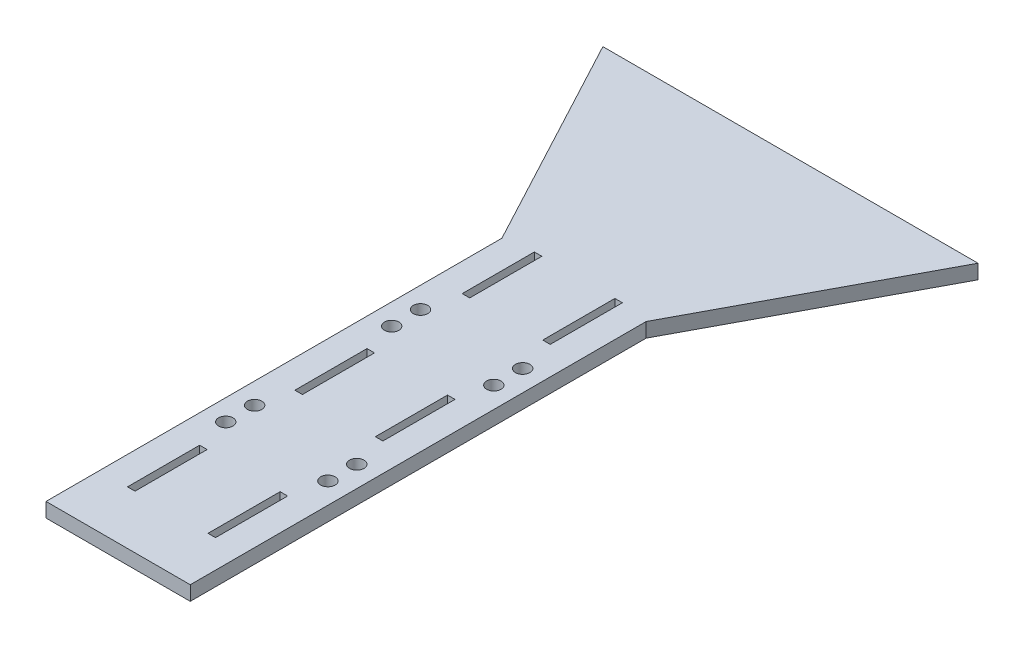
SolidWorks part; units mm, degrees
material "PC High Viscosity"
ref_plane "Front" through (0, 0, 0) normal (0, 0, 1) x (1, 0, 0)
ref_plane "Top" through (0, 0, 0) normal (0, 1, 0) x (1, 0, 0)
ref_plane "Right" through (0, 0, 0) normal (1, 0, 0) x (0, 0, -1)
sketch "Sketch1" plane through (0, 0, 0) normal (0, 1, 0) x (1, 0, 0)
  line L0 (-31.75, 0) -> (31.75, 0)
  line L1 (31.75, 0) -> (31.75, 200.66)
  line L2 (31.75, 200.66) -> (82.55, 295.91)
  line L3 (82.55, 295.91) -> (-82.55, 295.91)
  line L4 (-82.55, 295.91) -> (-31.75, 200.66)
  line L5 (-31.75, 200.66) -> (-31.75, 0)
  point P4 (0, 0)
  dimension "D1" = 63.5
  dimension "D2" = 200.66
  dimension "D3" = 95.25
  dimension "D4" = 165.1
extrude "Boss-Extrude1" add sketch "Sketch1" along normal blind 6.35
sketch "Sketch2" plane through (0, 6.35, 0) normal (0, 1, 0) x (1, 0, 0)
  line L0 (-19.304, 199.39) -> (-19.304, 173.99) construction
  line L1 (-19.304, 173.99) -> (-16.129, 173.99) construction
  line L2 (-16.129, 173.99) -> (-16.129, 199.39) construction
  line L3 (-16.129, 199.39) -> (-19.304, 199.39) construction
  line L4 (-19.304, 125.73) -> (-19.304, 100.33) construction
  line L5 (-19.304, 100.33) -> (-16.129, 100.33) construction
  line L6 (-16.129, 100.33) -> (-16.129, 125.73) construction
  line L7 (-16.129, 125.73) -> (-19.304, 125.73) construction
  line L12 (-19.304, 52.07) -> (-19.304, 26.67) construction
  line L13 (-19.304, 26.67) -> (-16.129, 26.67) construction
  line L14 (-16.129, 26.67) -> (-16.129, 52.07) construction
  line L15 (-16.129, 52.07) -> (-19.304, 52.07) construction
  line L20 (-19.304, 199.39) -> (-19.304, 173.99) construction
  line L21 (-19.304, 173.99) -> (-16.129, 173.99) construction
  line L22 (-16.129, 173.99) -> (-16.129, 199.39) construction
  line L23 (-16.129, 199.39) -> (-19.304, 199.39) construction
  line L24 (-19.304, 125.73) -> (-19.304, 100.33) construction
  line L25 (-19.304, 100.33) -> (-16.129, 100.33) construction
  line L26 (-16.129, 100.33) -> (-16.129, 125.73) construction
  line L27 (-16.129, 125.73) -> (-19.304, 125.73) construction
  line L32 (-19.304, 52.07) -> (-19.304, 26.67) construction
  line L33 (-19.304, 26.67) -> (-16.129, 26.67) construction
  line L34 (-16.129, 26.67) -> (-16.129, 52.07) construction
  line L35 (-16.129, 52.07) -> (-19.304, 52.07) construction
  line L36 (16.129, 52.07) -> (16.129, 26.67) construction
  line L37 (16.129, 26.67) -> (19.304, 26.67) construction
  line L38 (19.304, 26.67) -> (19.304, 52.07) construction
  line L39 (19.304, 52.07) -> (16.129, 52.07) construction
  line L44 (16.129, 125.73) -> (16.129, 100.33) construction
  line L45 (16.129, 100.33) -> (19.304, 100.33) construction
  line L46 (19.304, 100.33) -> (19.304, 125.73) construction
  line L47 (19.304, 125.73) -> (16.129, 125.73) construction
  line L48 (16.129, 199.39) -> (16.129, 173.99) construction
  line L49 (16.129, 173.99) -> (19.304, 173.99) construction
  line L50 (19.304, 173.99) -> (19.304, 199.39) construction
  line L51 (19.304, 199.39) -> (16.129, 199.39) construction
  line L56 (16.129, 52.07) -> (16.129, 26.67) construction
  line L57 (16.129, 26.67) -> (19.304, 26.67) construction
  line L58 (19.304, 26.67) -> (19.304, 52.07) construction
  line L59 (19.304, 52.07) -> (16.129, 52.07) construction
  line L60 (16.129, 125.73) -> (16.129, 100.33) construction
  line L61 (16.129, 100.33) -> (19.304, 100.33) construction
  line L62 (19.304, 100.33) -> (19.304, 125.73) construction
  line L63 (19.304, 125.73) -> (16.129, 125.73) construction
  line L68 (16.129, 199.39) -> (16.129, 173.99) construction
  line L69 (16.129, 173.99) -> (19.304, 173.99) construction
  line L70 (19.304, 173.99) -> (19.304, 199.39) construction
  line L71 (19.304, 199.39) -> (16.129, 199.39) construction
  line L72 (-19.3675, 23.495) -> (-19.304, 26.67) construction
  line L73 (-19.3675, 23.495) -> (-16.0655, 23.495)
  line L74 (-19.3675, 23.495) -> (-19.3675, 55.245)
  line L75 (-19.3675, 55.245) -> (-16.0655, 55.245)
  line L76 (-16.0655, 23.495) -> (-16.0655, 55.245)
  line L77 (-19.3675, 97.155) -> (-16.0655, 97.155)
  line L78 (-19.3675, 97.155) -> (-19.3675, 128.905)
  line L79 (-19.3675, 128.905) -> (-16.0655, 128.905)
  line L80 (-16.0655, 97.155) -> (-16.0655, 128.905)
  line L81 (-19.3675, 170.815) -> (-16.0655, 170.815)
  line L82 (-19.3675, 170.815) -> (-19.3675, 202.565)
  line L83 (-19.3675, 202.565) -> (-16.0655, 202.565)
  line L84 (-16.0655, 170.815) -> (-16.0655, 202.565)
  line L85 (16.0655, 23.495) -> (19.3675, 23.495)
  line L86 (16.0655, 23.495) -> (16.0655, 55.245)
  line L87 (16.0655, 55.245) -> (19.3675, 55.245)
  line L88 (19.3675, 23.495) -> (19.3675, 55.245)
  line L89 (16.0655, 97.155) -> (19.3675, 97.155)
  line L90 (16.0655, 97.155) -> (16.0655, 128.905)
  line L91 (16.0655, 128.905) -> (19.3675, 128.905)
  line L92 (19.3675, 97.155) -> (19.3675, 128.905)
  line L93 (16.0655, 170.815) -> (19.3675, 170.815)
  line L94 (16.0655, 170.815) -> (16.0655, 202.565)
  line L95 (16.0655, 202.565) -> (19.3675, 202.565)
  line L96 (19.3675, 170.815) -> (19.3675, 202.565)
  line L97 (-16.129, 52.07) -> (-16.0655, 55.245) construction
  line L98 (-19.3675, 97.155) -> (-19.304, 100.33) construction
  line L99 (-16.129, 125.73) -> (-16.0655, 128.905) construction
  line L100 (-19.304, 173.99) -> (-19.3675, 170.815) construction
  line L101 (-16.129, 199.39) -> (-16.0655, 202.565) construction
  line L102 (16.129, 199.39) -> (16.0655, 202.565) construction
  line L103 (19.304, 173.99) -> (19.3675, 170.815) construction
  line L104 (16.129, 125.73) -> (16.0655, 128.905) construction
  line L105 (19.304, 100.33) -> (19.3675, 97.155) construction
  line L106 (16.129, 52.07) -> (16.0655, 55.245) construction
  line L107 (19.304, 26.67) -> (19.3675, 23.495) construction
  dimension "D1" = 3.302
  dimension "D2" = 31.75
extrude "Cut-Extrude1" cut sketch "Sketch2" against normal through all
sketch "Sketch3" plane through (0, 6.35, 0) normal (0, 1, 0) x (1, 0, 0)
  line L0 (0, 295.91) -> (0, 149.225) construction
  line L1 (82.55, 295.91) -> (-82.55, 295.91) construction
  line L2 (0, 149.225) -> (-31.75, 149.225) construction
  line L3 (-31.75, 200.66) -> (-31.75, 0) construction
  line L5 (-22.479, 69.85) -> (-22.479, 82.55) construction
  line L6 (-19.304, 128.27) -> (-19.304, 171.45) construction
  line L9 (-31.75, 0) -> (31.75, 0) construction
  circle A0 centre (-22.479, 155.575) radius 3.175
  circle A1 centre (-22.479, 142.875) radius 3.175
  circle A2 centre (22.479, 142.875) radius 3.175
  circle A3 centre (22.479, 155.575) radius 3.175
  circle A6 centre (-22.479, 69.85) radius 3.175
  circle A7 centre (-22.479, 82.55) radius 3.175
  circle A8 centre (22.479, 69.85) radius 3.175
  circle A9 centre (22.479, 82.55) radius 3.175
  point P19 (-22.479, 152.6514)
  point P20 (-22.479, 156.7367)
  point P21 (0, 0)
  point P22 (0, 0)
  point P23 (0, 0)
  point P24 (0, 0)
  point P32 (-22.479, 76.2)
  dimension "D2" = 6.35
  dimension "D4" = 12.7
  dimension "D3" = 12.7
  dimension "D1" = 76.2
  dimension "D5" = 149.225
extrude "Cut-Extrude2" cut sketch "Sketch3" against normal through all
